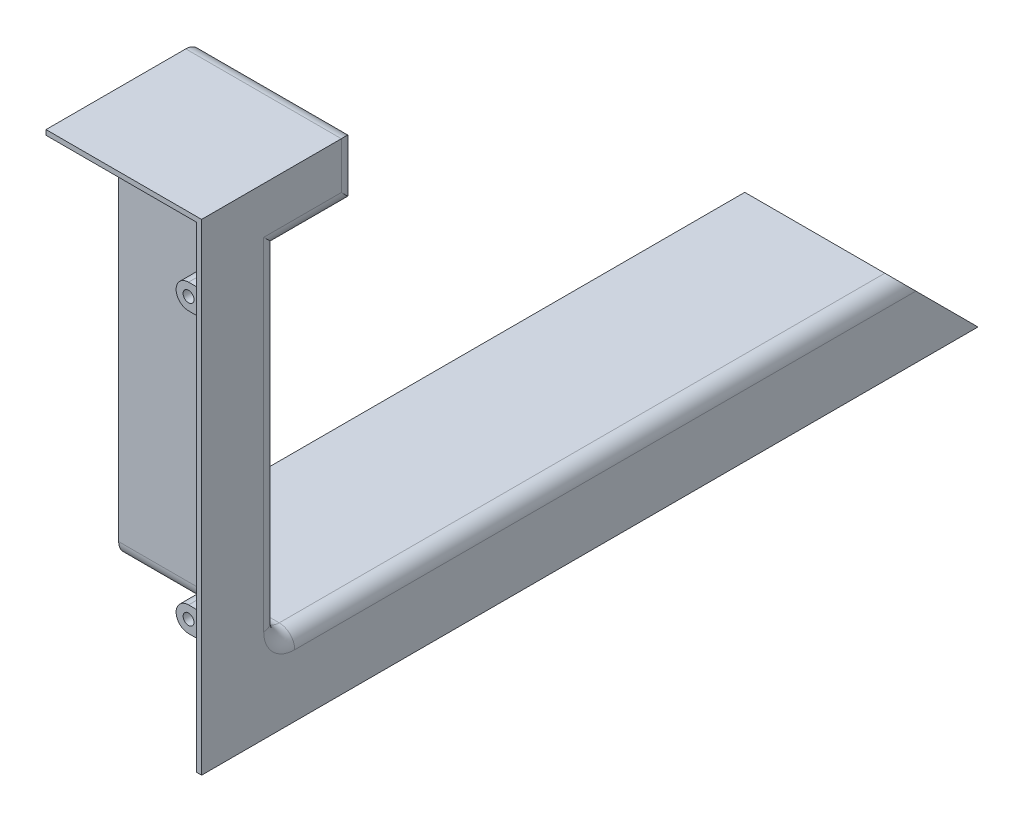
SolidWorks part; units mm, degrees
ref_plane "Front Plane" through (0, 0, 0) normal (0, 0, 1) x (1, 0, 0)
ref_plane "Top Plane" through (0, 0, 0) normal (0, 1, 0) x (1, 0, 0)
ref_plane "Right Plane" through (0, 0, 0) normal (1, 0, 0) x (0, 0, -1)
sketch "Sketch1" plane through (0, 0, 0) normal (1, 0, 0) x (0, 0, -1)
  line L0 (0, 155) -> (0, 0)
  line L1 (0, 0) -> (250, 0)
  line L2 (250, 0) -> (225, 25)
  line L3 (225, 25) -> (25, 25)
  line L4 (25, 25) -> (25, 135)
  line L5 (25, 155) -> (0, 155)
  line L6 (25, 155) -> (50, 155)
  line L7 (50, 155) -> (50, 135)
  line L8 (50, 135) -> (25, 135)
  dimension "D1" = 155
  dimension "D2" = 250
  dimension "D3" = 25
  dimension "D4" = 25
  dimension "D5" = 45
  dimension "D6" = 25
  dimension "D7" = 20
  dimension "D8" = 25
extrude "Boss-Extrude1" add sketch "Sketch1" along normal blind 1.6
sketch "Sketch2" plane through (0, 0, 0) normal (1, 0, 0) x (0, 0, -1)
  line L0 (225, 25) -> (25, 25) construction
  line L1 (25, 25) -> (25, 135) construction
  line L2 (25, 135) -> (50, 135) construction
  line L3 (50, 135) -> (50, 155) construction
  line L4 (50, 155) -> (0, 155) construction
  line L5 (225, 25) -> (25, 25)
  line L6 (25, 25) -> (25, 135)
  line L7 (25, 135) -> (50, 135)
  line L8 (50, 135) -> (50, 155)
  line L9 (50, 155) -> (0, 155)
  line L10 (225, 25) -> (225, 1.6)
  line L11 (223.4, 0) -> (250, 0)
  line L12 (48.4, 153.4) -> (0, 153.4)
  line L13 (48.4, 136.6) -> (48.4, 153.4)
  line L14 (23.4, 136.6) -> (48.4, 136.6)
  line L15 (23.4, 23.4) -> (23.4, 136.6)
  line L16 (223.4, 23.4) -> (23.4, 23.4)
  line L17 (223.4, 23.4) -> (223.4, 0)
  line L18 (0, 155) -> (0, 153.4)
  line L21 (225, 1.6) -> (248.4, 1.6)
  line L22 (250, 0) -> (225, 25) construction
  line L23 (248.4, 1.6) -> (250, 0)
  line L25 (225, 25) -> (225, 0) construction
  dimension "D2" = 1.6
  dimension "D1" = 1.6
extrude "Boss-Extrude2" add sketch "Sketch2" against normal blind 48.5
fillet "Fillet1" radius 5 12 edges at (1.6, 80, -25) (0, 80, -23.4) (1.6, 145, -50) (1.6, 135, -37.5) (0, 145, -48.4) (0, 136.6, -35.9) (-23.45, 155, -50) (-24.25, 153.4, -48.4) (-24.25, 23.4, -23.4) (-23.45, 25, -25) (1.6, 25, -125) (0, 23.4, -123.4)
fillet "Fillet2" radius 5 2 edges at (0, 12.633, -225) (0, 1.6, -236.7)
ref_plane "Plane1" through (0, 6, 0) normal (0, -1, 0) x (-1, 0, 0)
sketch "Sketch3" plane through (0, 6, 0) normal (0, -1, 0) x (1, 0, 0)
  line L0 (-48.5, -223.4) -> (-48.5, -144.7093) construction
  line L1 (0, -34.5) -> (-1.6381, -34.5)
  line L2 (-1.6381, -32.0028) -> (0, -31.5)
  line L3 (-1.6381, -211.5) -> (0, -211.5)
  line L4 (0, -214.5) -> (-1.6381, -214.9988)
  line L5 (0, -31.5) -> (0, -34.5)
  line L6 (0, -211.5) -> (0, -214.5)
  line L13 (-98.6, 0) -> (-98.6, -250)
  line L14 (-98.6, -250) -> (-48.5, -250)
  line L15 (-48.5, -250) -> (-48.5, -223.4)
  line L16 (-48.5, -223.4) -> (-97, -223.4)
  line L17 (-97, -223.4) -> (-97, 0)
  line L18 (-90, -33.4) -> (-7.114, -33.4) construction
  line L19 (-7.114, -213.4) -> (-90, -213.4) construction
  line L20 (0, -28.4) -> (0, -223.4) construction
  line L24 (-97, 0) -> (-98.6, 0)
  line L25 (-98.6, 0) -> (-98.6, -250) construction
  line L26 (-98.6, -250) -> (-48.5, -250) construction
  line L27 (-48.5, -250) -> (-48.5, -223.4) construction
  line L28 (-48.5, -223.4) -> (-97, -223.4) construction
  line L29 (-97, -223.4) -> (-97, 0) construction
  line L36 (-97, 0) -> (-98.6, 0) construction
  arc A0 (-3.9375, -35.5731) -> (-1.6381, -34.5) centre (-1.6381, -37.5) cw
  arc A1 (-3.9375, -35.5731) -> (-4.3217, -30.7513) centre (-7.114, -33.4) cw
  arc A2 (-1.6381, -32.0028) -> (-4.3217, -30.7513) centre (-1.6381, -28.5) cw
  arc A3 (-1.6381, -211.5) -> (-3.9361, -210.4286) centre (-1.6381, -208.5) cw
  arc A4 (-3.5218, -215.8545) -> (-3.9361, -210.4286) centre (-7.114, -213.4) cw
  arc A5 (-3.5218, -215.8545) -> (-1.6381, -214.9988) centre (-1.6381, -217.5) cw
  circle A18 centre (-7.114, -213.4) radius 1.5
  circle A19 centre (-90, -213.4) radius 1.5 construction
  circle A20 centre (-7.114, -33.4) radius 1.5
  circle A21 centre (-90, -33.4) radius 1.5 construction
  dimension "D1" = 0
extrude "Boss-Extrude3" add sketch "Sketch3" against normal up to next contours L2 A2 A1 A0 L1 A20 | A4 A5 L4 L3 A3 A18 region at (-0.819, 6, -34.366) region at (-0.819, 6, -211.6439)
ref_plane "Plane2" through (0, 0, -3.9) normal (0, 0, 1) x (1, 0, 0)
sketch "Sketch4" plane through (0, 0, -3.9) normal (0, 0, 1) x (1, 0, 0)
  line L1 (-6.5, 131.5) -> (0, 131.5)
  line L3 (-6.5, 123.5) -> (0, 123.5)
  line L4 (0, 131.5) -> (0, 123.5)
  line L5 (-6.5, 41.5) -> (0, 41.5)
  line L7 (-6.5, 33.5) -> (0, 33.5)
  line L8 (0, 41.5) -> (0, 33.5)
  circle A0 centre (-6.5, 127.5) radius 1.75 construction
  circle A1 centre (-6.5, 37.5) radius 1.75 construction
  circle A2 centre (-6.5, 127.5) radius 1.75
  circle A3 centre (-6.5, 37.5) radius 1.75
  arc A4 (-6.5, 131.5) -> (-6.5, 123.5) centre (-6.5, 127.5) ccw
  arc A5 (-6.5, 41.5) -> (-6.5, 33.5) centre (-6.5, 37.5) ccw
  dimension "D1" = 8
extrude "Boss-Extrude4" add sketch "Sketch4" against normal up to surface (19.5 mm away) up to face at (-26.75, 82.5, -23.4)
equation "\"D2@Sketch2\"=\"D1@Sketch2\""
